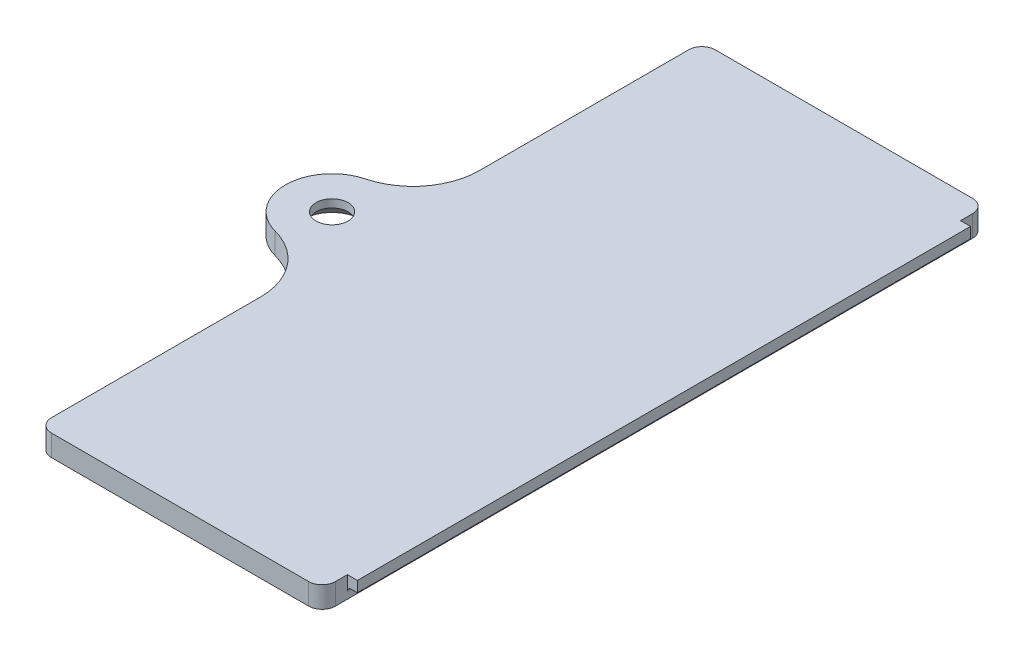
SolidWorks part; units mm, degrees
ref_plane "Front Plane" through (0, 0, 0) normal (0, 0, 1) x (1, 0, 0)
ref_plane "Top Plane" through (0, 0, 0) normal (0, 1, 0) x (1, 0, 0)
ref_plane "Right Plane" through (0, 0, 0) normal (1, 0, 0) x (0, 0, -1)
sketch "Door Plate 1.6 + screw ear (R5 / R3.5) Sketch" plane through (0, 0, 0) normal (0, 1, 0) x (1, 0, 0)
  line L0 (9.35, 15.1) -> (30.65, 15.1)
  line L1 (30.65, 15.1) -> (30.65, 64.9)
  line L2 (30.65, 64.9) -> (9.35, 64.9)
  line L3 (9.35, 64.9) -> (9.35, 48.2236)
  line L4 (9.35, 31.7764) -> (9.35, 15.1)
  arc A0 (9.35, 31.7764) -> (5.6147, 36.6138) centre (4.35, 31.7764) ccw
  arc A1 (5.6147, 36.6138) -> (5.6147, 43.3862) centre (6.5, 40) cw
  arc A2 (5.6147, 43.3862) -> (9.35, 48.2236) centre (4.35, 48.2236) ccw
extrude "Door Plate 1.6 + screw ear (R5 / R3.5)" add sketch "Door Plate 1.6 + screw ear (R5 / R3.5) Sketch" along normal blind 1.6
ref_plane "Hook Flange Plane y0.8" through (0, 0.8, 0) normal (0, 1, 0) x (1, 0, 0)
sketch "Hook Flange 0.75 x 0.8 (inner-face plane) Sketch" plane through (0, 0.8, 0) normal (0, 1, 0) x (1, 0, 0)
  line L0 (30.5, 17) -> (31.4, 17)
  line L1 (31.4, 17) -> (31.4, 63)
  line L2 (31.4, 63) -> (30.5, 63)
  line L3 (30.5, 63) -> (30.5, 17)
extrude "Hook Flange 0.75 x 0.8 (inner-face plane)" add sketch "Hook Flange 0.75 x 0.8 (inner-face plane) Sketch" along normal blind 0.8
sketch "Screw Hole 2.4 (free) Sketch" plane through (0, 0, 0) normal (0, 1, 0) x (1, 0, 0)
  circle A0 centre (6.5, 40) radius 1.2
extrude "Screw Hole 2.4 (free)" cut sketch "Screw Hole 2.4 (free) Sketch" along normal through all
chamfer "Screw CSK 90deg (M2)" distance 1 angle 45 1 edges at (6.5, 0, -38.8)
fillet "Door Corners R1 (print)" radius 1 4 edges at (9.35, 0.8, -64.9) (30.65, 0.8, -64.9) (30.65, 0.8, -15.1) (9.35, 0.8, -15.1)
fillet "Hook Flange Root Fillet R0.3" radius 0.3 1 edges at (30.65, 0.8, -40)
